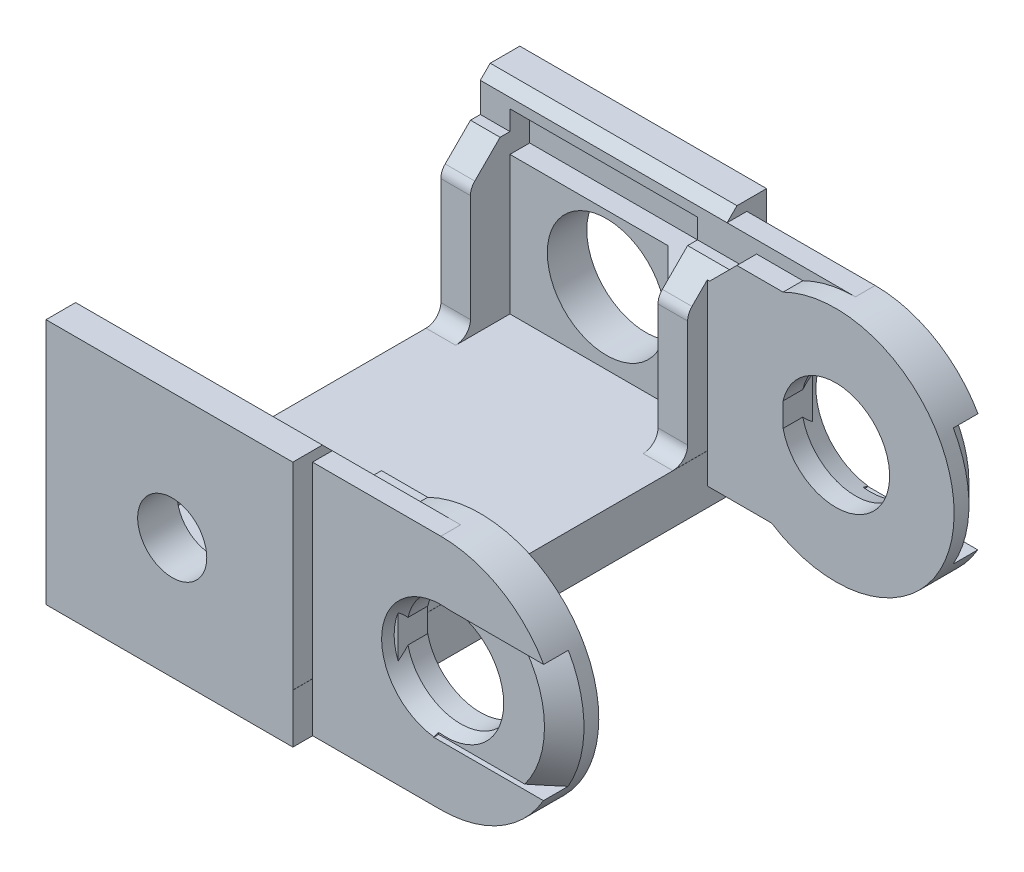
SolidWorks part; units mm, degrees
ref_plane "Front" through (0, 0, 0) normal (0, 0, 1) x (1, 0, 0)
ref_plane "Top" through (0, 0, 0) normal (0, 1, 0) x (1, 0, 0)
ref_plane "Right" through (0, 0, 0) normal (1, 0, 0) x (0, 0, -1)
sketch "Эскиз1" plane through (0, 0, 0) normal (0, 0, 1) x (1, 0, 0)
  line L1 (-38.7795, 23.7195) -> (-13.7795, 23.7195)
  line L2 (-38.7795, 23.7195) -> (-38.7795, -1.2805)
  line L3 (-38.7795, -1.2805) -> (-13.7795, -1.2805)
  line L4 (-13.7795, 23.7195) -> (-13.7795, -1.2805)
  dimension "D1" = 25
  dimension "D2" = 25
extrude "Бобышка-Вытянуть1" add sketch "Эскиз1" along normal blind 4
sketch "Эскиз2" plane through (0, 0, 0) normal (0, 0, -1) x (-1, 0, 0)
  line L0 (38.7795, 22.7195) -> (62.7795, 22.7195)
  line L1 (38.7795, 23.7195) -> (38.7795, -1.2805) construction
  line L3 (62.7795, 22.7195) -> (62.7795, -1.2805)
  line L4 (62.7795, -1.2805) -> (38.7795, -1.2805)
  line L5 (38.7795, -1.2805) -> (38.7795, 22.7195)
  dimension "D1" = 24
  dimension "D2" = 24
extrude "Бобышка-Вытянуть2" add sketch "Эскиз2" against normal blind 3.5
sketch "Эскиз3" plane through (0, 0, 3.5) normal (0, 0, 1) x (1, 0, 0)
  line L1 (-38.7795, -1.2805) -> (-62.7795, -1.2805) construction
  line L2 (-62.7795, -1.2805) -> (-62.7795, 22.7195) construction
  circle A0 centre (-50.7795, 10.7195) radius 5.625
  dimension "D2" = 11.25
  dimension "D1" = 12
  dimension "D3" = 12
sketch "Эскиз5" plane through (0, 0, 4) normal (0, 0, 1) x (1, 0, 0)
  line L0 (-18.982, 10.7195) -> (-0.7795, 10.7195) construction
  line L1 (-18.982, 22.7195) -> (-0.7795, 22.7195)
  line L2 (-18.982, -1.2805) -> (-0.7795, -1.2805)
  line L3 (-13.7795, -1.2805) -> (-13.7795, 23.7195) construction
  line L4 (-38.7795, -1.2805) -> (-13.7795, -1.2805) construction
  arc A0 (-18.982, 22.7195) -> (-18.982, -1.2805) centre (-18.982, 10.7195) ccw
  arc A1 (-0.7795, -1.2805) -> (-0.7795, 22.7195) centre (-0.7795, 10.7195) ccw
  point P2 (-9.8808, 10.7195)
  dimension "D1" = 13
  dimension "D2" = 12
  dimension "D3" = 12
extrude "Бобышка-Вытянуть4" add sketch "Эскиз5" against normal blind 2
sketch "Эскиз6" plane through (0, 0, 2) normal (0, 0, -1) x (-1, 0, 0)
  circle A0 centre (0.7795, 10.7195) radius 5
  arc A1 (0.7795, 22.7195) -> (0.7795, -1.2805) centre (0.7795, 10.7195) ccw construction
extrude "Вырез-Вытянуть2" cut sketch "Эскиз6" against normal blind 10
sketch "Эскиз8" plane through (0, 0, 4) normal (0, 0, 1) x (1, 0, 0)
  line L5 (-38.7795, 3.7195) -> (-35.7795, 3.7195)
  line L6 (-38.7795, -1.2805) -> (-13.7795, -1.2805)
  line L7 (-38.7795, -1.2805) -> (-38.7795, 3.7195)
  line L9 (-13.7795, -1.2805) -> (-13.7795, 3.7195)
  line L10 (-35.7795, 3.7195) -> (-35.7795, 0.7195)
  line L11 (-35.7795, 0.7195) -> (-16.7795, 0.7195)
  line L12 (-16.7795, 0.7195) -> (-16.7795, 3.7195)
  line L13 (-16.7795, 3.7195) -> (-13.7795, 3.7195)
  line L14 (-13.7795, 22.7195) -> (-13.7795, 23.7195) construction
  dimension "D1" = 3
  dimension "D2" = 3
  dimension "D3" = 2
  dimension "D4" = 5
  dimension "D5" = 5
extrude "Бобышка-Вытянуть6" add sketch "Эскиз8" along normal blind 20
sketch "Эскиз9" plane through (0, 0, 4) normal (0, 0, 1) x (1, 0, 0)
  line L0 (-38.7795, 23.7195) -> (-38.7795, 3.7195) construction
  line L1 (-35.7795, 20.7195) -> (-16.7795, 20.7195)
  line L2 (-35.7795, 20.7195) -> (-35.7795, 17.7195)
  line L3 (-35.7795, 17.7195) -> (-16.7795, 17.7195)
  line L4 (-16.7795, 20.7195) -> (-16.7795, 17.7195)
  line L5 (-13.7795, 22.7195) -> (-13.7795, 23.7195) construction
  line L6 (-13.7795, 23.7195) -> (-38.7795, 23.7195) construction
  dimension "D1" = 3
  dimension "D2" = 3
  dimension "D3" = 3
  dimension "D4" = 6
extrude "Вырез-Вытянуть4" cut sketch "Эскиз9" against normal blind 2
chamfer "Фаска2" distance 1 angle 45 1 edges at (-26.2795, 20.7195, 4)
chamfer "Фаска3" distance 1 angle 75 1 edges at (-5.7795, 10.7195, 2) first distance on face at (-5.7795, 10.7195, 2)
chamfer "Фаска4" distance 1 angle 45 1 edges at (-26.2795, 23.7195, 4)
sketch "Эскиз11" plane through (0, 3.7195, 0) normal (0, 1, 0) x (1, 0, 0)
  line L0 (-35.7795, -24) -> (-35.7795, -4) construction
  line L1 (-38.7795, -4) -> (-35.7795, -4)
  line L2 (-38.7795, -4) -> (-38.7795, -8)
  line L3 (-38.7795, -8) -> (-35.7795, -8)
  line L4 (-35.7795, -4) -> (-35.7795, -8)
  dimension "D1" = 4
extrude "Бобышка-Вытянуть7" add sketch "Эскиз11" along normal blind 16
pattern_linear "Линейный массив1" count 2 spacing 22 along (1, 0, 0) of "Бобышка-Вытянуть7"
chamfer "Фаска6" distance 3 angle 45 2 edges at (-15.2795, 19.7195, 8) (-37.2795, 19.7195, 8)
fillet "Скругление2" radius 1.5 4 edges at (-15.2795, 3.7195, 8) (-15.2795, 16.7195, 8) (-37.2795, 16.7195, 8) (-37.2795, 3.7195, 8)
sketch "Эскиз13" plane through (0, 0, 4) normal (0, 0, 1) x (1, 0, 0)
  circle A0 centre (-50.993, 10.9769) radius 3.5
extrude "Вырез-Вытянуть6" cut sketch "Эскиз13" against normal blind 10
pattern_linear "Линейный массив2" count 2 spacing 25 along (1, 0, 0) of "Вырез-Вытянуть6"
chamfer "Фаска7" distance 3 angle 45 2 edges at (-38.7795, 10.7195, 3.5) (-16.7795, 9.2195, 4)
sketch "Эскиз16" plane through (0, 0, 4) normal (0, 0, 1) x (1, 0, 0)
  circle A0 centre (-0.7795, 10.7195) radius 5.4641
  circle A1 centre (-0.7795, 10.7195) radius 12
extrude "Бобышка-Вытянуть9" add sketch "Эскиз16" along normal blind 2
sketch "Эскиз17" plane through (0, 0, 6) normal (0, 0, 1) x (1, 0, 0)
  line L1 (-6.1084, 21.4714) -> (-13.7892, 21.4714)
  line L2 (-6.1084, 21.4714) -> (-6.1084, 0.6234)
  line L3 (-6.1084, 0.6234) -> (-13.7892, 0.6234)
  line L4 (-13.7892, 21.4714) -> (-13.7892, 0.6234)
  circle A0 centre (-0.7795, 10.7195) radius 12 construction
extrude "Бобышка-Вытянуть10" add sketch "Эскиз17" against normal blind 3
chamfer "Фаска8" distance 3 angle 45 1 edges at (-13.7892, 21.4714, 5)
sketch "Эскиз18" plane through (0, 0, 2) normal (0, 0, -1) x (-1, 0, 0)
  line L1 (1.5008, 16.676) -> (-12.7446, 16.676)
  line L2 (1.5008, 16.676) -> (1.5008, 4.7195)
  line L3 (1.5008, 4.7195) -> (-12.7446, 4.7195)
  line L4 (-12.7446, 16.676) -> (-12.7446, 4.7195)
  circle A0 centre (0.7795, 10.7195) radius 6 construction
extrude "Вырез-Вытянуть8" cut sketch "Эскиз18" against normal blind 0.5
chamfer "Фаска9" distance 2 angle 45 1 edges at (11.2204, 10.6944, 2.5)
mirror "Зеркальное отражение1" about plane through (0, 0, 24) normal (0, 0, -1) of bodies 121 109
sketch "Эскиз14" plane through (0, -1.2805, 0) normal (0, -1, 0) x (-1, 0, 0)
  line L0 (62.7795, 0) -> (13.7795, 0) construction
  line L1 (62.7795, -48) -> (13.768, -48)
  line L2 (62.7795, -48) -> (62.7795, 0)
  line L3 (62.7795, 0) -> (13.768, 0)
  line L4 (13.768, -48) -> (13.768, 0)
extrude "Бобышка-Вытянуть8" add sketch "Эскиз14" against normal blind 5
sketch "Эскиз15" plane through (0, 0, 0) normal (0, 0, -1) x (-1, 0, 0)
  circle A0 centre (50.993, 10.9769) radius 6
  circle A1 centre (25.993, 10.9769) radius 6
extrude "Вырез-Вытянуть7" cut sketch "Эскиз15" against normal blind 4
chamfer "Фаска10" distance 3 angle 45 2 edges at (-27.7795, 3.7195, 44) (-52.2795, 3.7195, 44.5)
sketch "Эскиз19" plane through (0, 0, 44.5) normal (0, 0, -1) x (-1, 0, 0)
  line L1 (62.7795, 22.7195) -> (60.6904, 22.7195)
  line L2 (62.7795, 22.7195) -> (62.7795, 0)
  line L3 (62.7795, 0) -> (60.6904, 0)
  line L4 (60.6904, 22.7195) -> (60.6904, 0)
extrude "Бобышка-Вытянуть11" add sketch "Эскиз19" along normal blind 15
chamfer "Фаска11" distance 10 angle 45 1 edges at (-61.735, 22.7195, 29.5)
sketch "Эскиз20" plane through (0, 0, 40) normal (0, 0, -1) x (-1, 0, 0)
  line L1 (13.7795, 16.0982) -> (16.8955, 16.0982)
  line L2 (13.7795, 16.0982) -> (13.7795, 2.3184)
  line L3 (13.7795, 2.3184) -> (16.8955, 2.3184)
  line L4 (16.8955, 16.0982) -> (16.8955, 2.3184)
  line L5 (35.7795, 16.0982) -> (38.95, 16.0982)
  line L6 (35.7795, 16.0982) -> (35.7795, 0.7032)
  line L7 (35.7795, 0.7032) -> (38.95, 0.7032)
  line L8 (38.95, 16.0982) -> (38.95, 0.7032)
extrude "Бобышка-Вытянуть12" add sketch "Эскиз20" along normal blind 10
sketch "Эскиз21" plane through (-13.7795, 0, 0) normal (1, 0, 0) x (0, 0, -1)
  line L0 (-30, 16.0982) -> (-30, 3.7195) construction
  circle A0 centre (-30, 14.2806) radius 10.018
extrude "Вырез-Вытянуть9" cut sketch "Эскиз21" against normal blind 100
sketch "Эскиз22" plane through (0, 0, 0) normal (0, 0, -1) x (-1, 0, 0)
  line L1 (38.7795, 23.7195) -> (70.4855, 23.7195)
  line L2 (38.7795, 23.7195) -> (38.7795, -8.6526)
  line L3 (38.7795, -8.6526) -> (70.4855, -8.6526)
  line L4 (70.4855, 23.7195) -> (70.4855, -8.6526)
extrude "Вырез-Вытянуть10" cut sketch "Эскиз22" against normal blind 100
